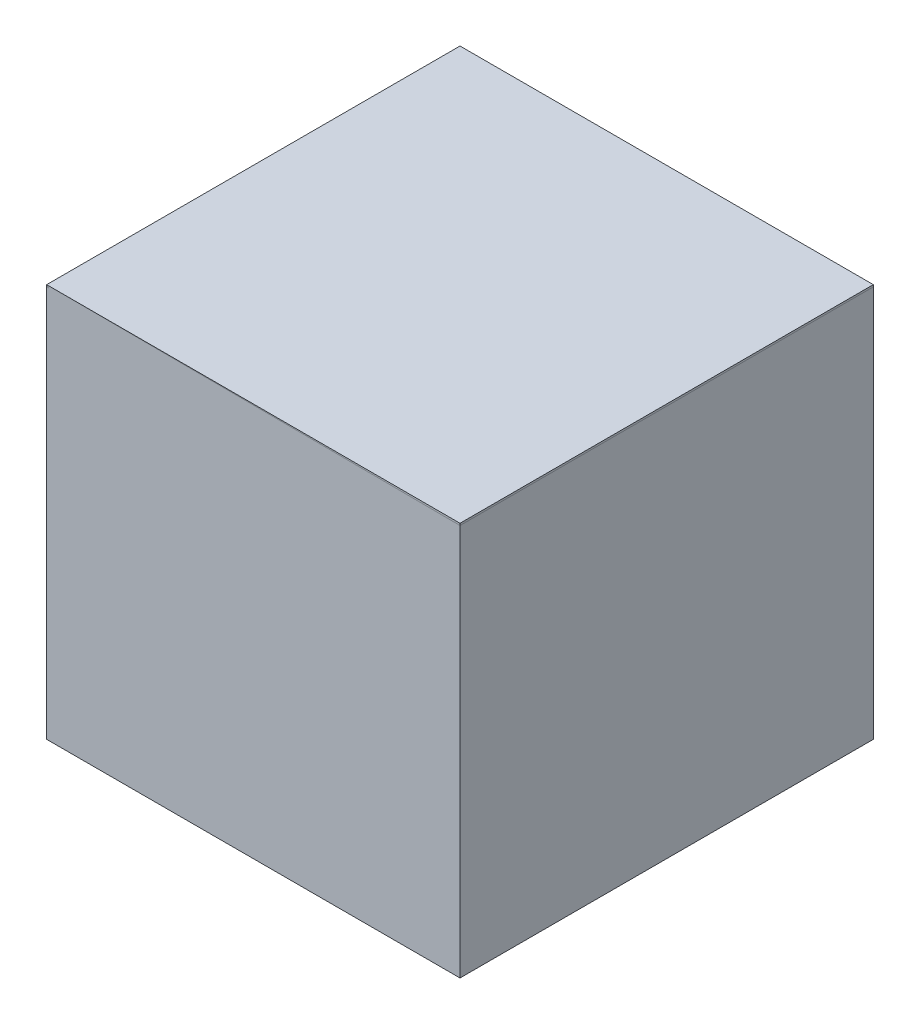
SolidWorks part; units mm, degrees
other "bottom outer panel"
ref_plane "Front Plane" through (0, 0, 0) normal (0, 0, 1) x (1, 0, 0)
ref_plane "Top Plane" through (0, 0, 0) normal (0, 1, 0) x (1, 0, 0)
ref_plane "Right Plane" through (0, 0, 0) normal (1, 0, 0) x (0, 0, -1)
sketch "Sketch1" plane through (0, 1025, 0) normal (0, 1, 0) x (1, 0, 0)
  line L9 (74.4937, 525.4529) -> (1124.5297, 525.4529)
  line L10 (74.4937, 525.4529) -> (74.4937, -524.5831)
  line L11 (74.4937, -524.5831) -> (1124.5297, -524.5831)
  line L12 (1124.5297, 525.4529) -> (1124.5297, -524.5831)
ref_plane "Plane1" through (0, 1030, 0) normal (0, 1, 0) x (1, 0, 0)
sketch "Sketch2" plane through (0, 1030, 0) normal (0, 1, 0) x (1, 0, 0)
  line L4 (1124.5297, 525.4529) -> (74.4937, 525.4529)
  line L5 (1124.5297, -524.5831) -> (1124.5297, 525.4529)
  line L6 (74.4937, -524.5831) -> (1124.5297, -524.5831)
  line L7 (74.4937, 525.4529) -> (74.4937, -524.5831)
  line L8 (1124.5297, 525.4529) -> (74.4937, 525.4529)
  line L9 (1124.5297, -524.5831) -> (1124.5297, 525.4529)
  line L10 (74.4937, -524.5831) -> (1124.5297, -524.5831)
  line L11 (74.4937, 525.4529) -> (74.4937, -524.5831)
  dimension "D1" = 0
extrude "Extrude-Thin1" add sketch "Sketch2" against normal blind 1010 thin thin type one direction wall 5
sketch "Sketch4" plane through (0, 1025, 0) normal (0, 1, 0) x (1, 0, 0)
  line L1 (69.4937, 530.4529) -> (1129.5297, 530.4529)
  line L2 (69.4937, 530.4529) -> (69.4937, -529.5831)
  line L3 (69.4937, -529.5831) -> (1129.5297, -529.5831)
  line L4 (1129.5297, 530.4529) -> (1129.5297, -529.5831)
extrude "Boss-Extrude1" add sketch "Sketch4" along normal blind 5 separate body
ref_axis "Axis1" through (69.4937, 1030, -530.4529) along (0.7071, 0, 0.7071)
ref_axis "Axis2" through (69.4937, 20, -530.4529) along (0.7071, 0, 0.7071)
ref_plane "Plane2" through (299.9733, 0, -299.9733) normal (-0.7071, 0, 0.7071) x (0.7071, 0, 0.7071)
ref_axis "Axis4" through (1129.5297, 1030, -530.4529) along (-0.7071, 0, 0.7071)
ref_axis "Axis5" through (69.4937, 20, 529.5831) along (0.7071, 0, -0.7071)
ref_plane "Plane3" through (299.5384, 0, 299.5384) normal (0.7071, 0, 0.7071) x (0.7071, 0, -0.7071)
